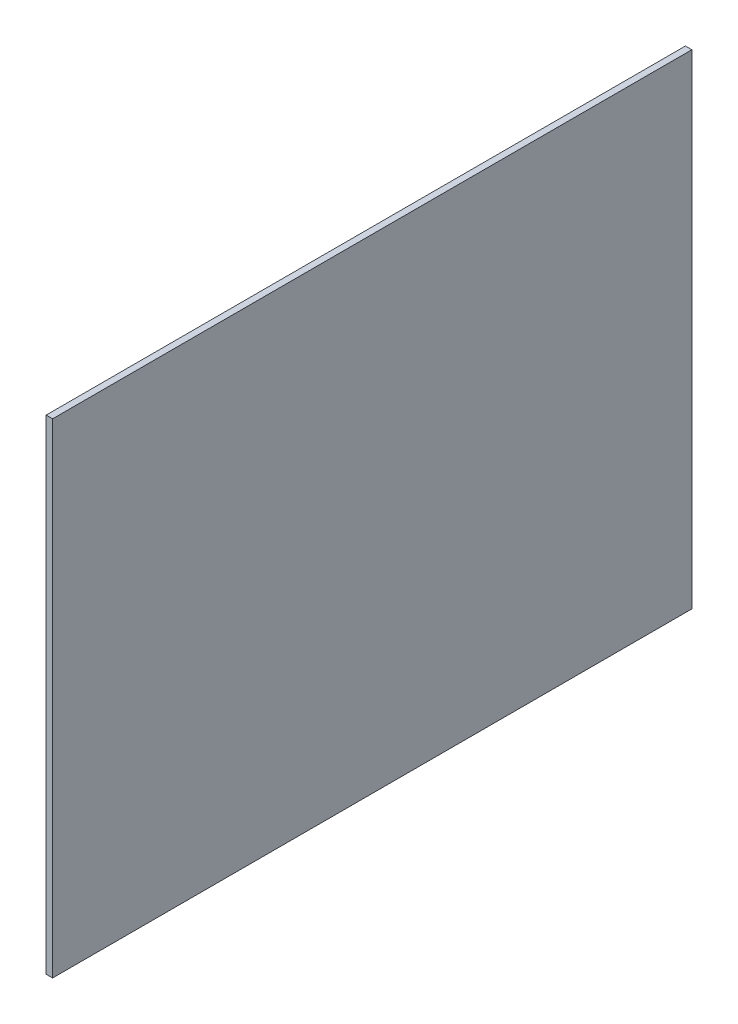
SolidWorks part; units mm, degrees
note: The reader was unsure of these and kept them because the rebuilt part matched: thickness of "Base-Flange1".
material "AISI 304"
ref_plane "Front Plane" through (0, 0, 0) normal (0, 0, 1) x (1, 0, 0)
ref_plane "Top Plane" through (0, 0, 0) normal (0, 1, 0) x (1, 0, 0)
ref_plane "Right Plane" through (0, 0, 0) normal (1, 0, 0) x (0, 0, -1)
sketch "Sketch1" plane through (0, 0, 0) normal (1, 0, 0) x (0, 0, -1)
  line L1 (99, -75) -> (-99, -75)
  line L2 (99, -75) -> (99, 75)
  line L3 (99, 75) -> (-99, 75)
  line L4 (-99, -75) -> (-99, 75)
  line L5 (99, -75) -> (-99, 75) construction
  line L6 (99, 75) -> (-99, -75) construction
  point P0 (0, 0)
  dimension "D1" = 150
  dimension "D2" = 198
base flange "Base-Flange1" sketch "Sketch1" thickness 2 reverse thickness direction no parameters "D1"=0.7366
sketch "Bend-Lines1" [suppressed] plane through (0, 0, 0) normal (0, 1, 0) x (1, 0, 0)
sketch "Bounding-Box1" [suppressed] plane through (0, 0, 0) normal (0, 1, 0) x (1, 0, 0)
sheet metal parameters "Sheet-Metal1" thickness 2 parameters "D1"=0.7366
flat pattern "Flat-Pattern1" [suppressed]
sketch "Bend-Lines2" plane through (0, 0, 0) normal (0, 1, 0) x (1, 0, 0)
sketch3d "Bounding-Box2" [suppressed]
  line L0 (-99, -75, 0) -> (99, -75, 0) construction
  line L1 (-99, 75, 0) -> (99, 75, 0) construction
  line L2 (-99, -75, 0) -> (-99, 75, 0) construction
  line L3 (99, -75, 0) -> (99, 75, 0) construction
equation "\"thickness 1\" = 2"
equation "\"thickness radius 1\"= 3.7366"
equation "\"thickness 2\"= 3"
equation "\"thickness 3\"= 1.2"
equation "\"thichness 4\"= 0.8"
equation "\"connecting flange\"= 35"
equation "\"connecting flange holes\"= 8"
equation "\"connecting flange hole gap\"= 100"
equation "\"main length\"= 1200"
equation "\"main width\"= 1200"
equation "\"cut out flange\"= 15"
equation "\"divider panel distance offset\"= 296"
equation "\"top panel slot length\"= 250"
equation "\"top panel slot width\"= 700"
equation "\"side panel length\"= 1200"
equation "\"side panel width\"= 950"
equation "\"access hatch cutout length\"= 400"
equation "\"access hatch cutout width\"= 600"
equation "\"access hatch cutout offset X\"= 100"
equation "\"access hatch cutout offset Y\"= 100"
equation "\"access hatch offset\"= 90"
equation "\"access hatch width\" = \"access hatch cutout width\" + \"access hatch offset\" * 2"
equation "\"access hatch length\" = \"access hatch cutout length\" + \"access hatch offset\" * 2"
equation "\"access hatch hole\"= 9"
equation "\"access hatch hole x gap\"= 350"
equation "\"access hatch hole y gap\"= 200"
equation "\"slotted panel length\" = \"main length\" + 100"
equation "\"slotted panel width\" = \"main width\""
equation "\"slot count x\"= 4"
equation "\"slot count y\"= 9"
equation "\"slot offset\" = \"water tray depth\""
equation "\"slot length\"= 30"
equation "\"slot width\"= 200"
equation "\"slot offset x\" = \"slot length\" + \"slot offset\""
equation "\"slot offset y\" = \"slot width\" + \"slot offset\""
equation "\"drift eliminator size offset\"= 5"
equation "\"drift eliminator depth\" = \"divider panel distance offset\""
equation "\"guide rail flange\"= 40"
equation "\"guid rail flange mount side\"= 20"
equation "\"guid rail back length\" = \"main width\" - \"guide rail flange\" * 2"
equation "\"splash plate length\"= 400"
equation "\"splash plate width\" = \"main width\""
equation "\"splash plate air gap\"= 200"
equation "\"splash plate slot count\"= 11"
equation "\"splash plate slot length\"= 50"
equation "\"splash plate slot height\"= 50"
equation "\"splash plate slot offset\"= 65"
equation "\"water tray depth\"= 150"
equation "\"water tray width\"= 200"
equation "\"water tray panel length\"= 473"
equation "\"water tray side panel width\"= \"water tray width\" - \"thickness 1\""
equation "\"water tray side panel length\"= \"water tray depth\""
equation "\"dimpled panel length\" = \"main length\" - 200 - \"water tray depth\"/2"
equation "\"dimpled panel top offset\" = \"water tray depth\"/2"
equation "\"dimpled panel width\" = \"main width\""
equation "\"dimple panel slot count\"= 36"
equation "\"dimple panel slot length\"= 8"
equation "\"dimple panel slot width\"= 8"
equation "\"dimple panel slot offset\"= 25"
equation "\"sump base flat section width\"= 300"
equation "\"sump upper depth\"= 300"
equation "\"sump depth\"= 550"
equation "\"leg length\" = \"sump depth\" + 150"
equation "\"leg width\"= 80"
equation "\"leg depth\"= 40"
equation "\"leg support plate size\" = \"leg width\" - \"thickness 2\" * 2"
equation "\"leg base plate thickness\"= 8"
equation "\"D1@Sketch1\"=\"water tray side panel length\""
equation "\"D2@Sketch1\"=\"water tray side panel width\""
equation "\"D7@Sheet-Metal1\"=\"thickness 1\""
